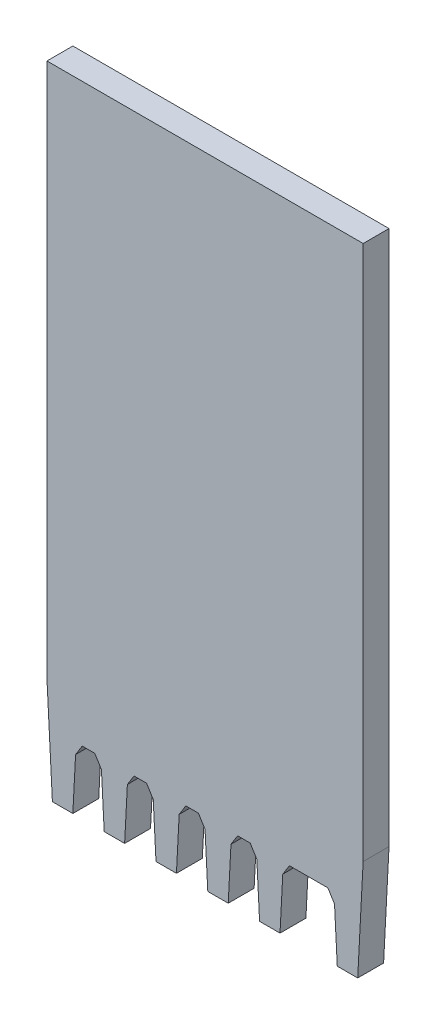
SolidWorks part; units mm, degrees
ref_plane "Front Plane" through (0, 0, 0) normal (0, 0, 1) x (1, 0, 0)
ref_plane "Top Plane" through (0, 0, 0) normal (0, 1, 0) x (1, 0, 0)
ref_plane "Right Plane" through (0, 0, 0) normal (1, 0, 0) x (0, 0, -1)
sketch "Sketch1" plane through (0, 0, 0) normal (0, 0, 1) x (1, 0, 0)
  line L0 (0, 0) -> (0, 37) construction
  line L1 (0, 37) -> (18.3124, 37) construction
  line L2 (18.3124, 37) -> (18.3124, 0) construction
  line L3 (18.3124, 0) -> (0, 0) construction
  line L4 (0, 3) -> (18.3124, 3) construction
  line L5 (0, 6) -> (18.3124, 6) construction
  line L6 (0.9062, 6) -> (0.9062, 0) construction
  line L7 (3.9062, 6) -> (3.9062, 0) construction
  line L8 (6.9062, 6) -> (6.9062, 0) construction
  line L9 (9.9062, 6) -> (9.9062, 0) construction
  line L10 (12.9062, 6) -> (12.9062, 0) construction
  line L11 (17.4062, 6) -> (17.4062, 0) construction
  line L12 (0.9062, 3) -> (3.9062, 3) construction
  line L13 (3.9062, 3) -> (6.9062, 3) construction
  line L14 (6.9062, 3) -> (9.9062, 3) construction
  line L15 (9.9062, 3) -> (12.9062, 3) construction
  line L16 (12.9062, 3) -> (17.4062, 3) construction
  line L17 (0.9062, 3) -> (0, 3) construction
  line L18 (17.4062, 3) -> (18.3124, 3) construction
  line L19 (2.4062, 3) -> (2.4062, 0) construction
  line L20 (5.4062, 3) -> (5.4062, 0) construction
  line L21 (8.4062, 3) -> (8.4062, 0) construction
  line L22 (11.4062, 3) -> (11.4062, 0) construction
  line L23 (15.1562, 3) -> (15.1562, 0) construction
  line L24 (14.4062, 3.75) -> (15.9062, 3.75) construction
  line L25 (0, 6) -> (0.3144, 0)
  line L26 (0.3144, 0) -> (1.4979, 0)
  line L27 (1.4979, 0) -> (1.6572, 3.0393)
  line L28 (3.1552, 3.0393) -> (3.3144, 0)
  line L29 (3.3144, 0) -> (4.4979, 0)
  line L30 (4.4979, 0) -> (4.6572, 3.0393)
  line L31 (6.1552, 3.0393) -> (6.3144, 0)
  line L32 (6.3144, 0) -> (7.4979, 0)
  line L33 (7.4979, 0) -> (7.6572, 3.0393)
  line L34 (9.1552, 3.0393) -> (9.3144, 0)
  line L35 (9.3144, 0) -> (10.4979, 0)
  line L36 (10.4979, 0) -> (10.6572, 3.0393)
  line L37 (12.1552, 3.0393) -> (12.3144, 0)
  line L38 (12.3144, 0) -> (13.4979, 0)
  line L39 (13.4979, 0) -> (13.6572, 3.0393)
  line L40 (16.6552, 3.0393) -> (16.8144, 0)
  line L41 (16.8144, 0) -> (17.9979, 0)
  line L42 (17.9979, 0) -> (18.3124, 6)
  line L44 (1.6572, 3.0393) -> (2.0426, 3.656)
  line L45 (0, 6) -> (0, 37)
  line L46 (0, 37) -> (18.3124, 37)
  line L47 (18.3124, 37) -> (18.3124, 6)
  line L48 (9.1562, 37) -> (9.1562, 6) construction
  line L49 (2.0426, 3.656) -> (2.7698, 3.656)
  line L50 (2.7698, 3.656) -> (3.1552, 3.0393)
  line L51 (4.6572, 3.0393) -> (5.0426, 3.656)
  line L52 (5.0426, 3.656) -> (5.7698, 3.656)
  line L53 (5.7698, 3.656) -> (6.1552, 3.0393)
  line L54 (7.6572, 3.0393) -> (8.0426, 3.656)
  line L55 (8.0426, 3.656) -> (8.7698, 3.656)
  line L56 (8.7698, 3.656) -> (9.1552, 3.0393)
  line L57 (10.6572, 3.0393) -> (11.0426, 3.656)
  line L58 (11.0426, 3.656) -> (11.7698, 3.656)
  line L59 (11.7698, 3.656) -> (12.1552, 3.0393)
  line L60 (13.6572, 3.0393) -> (14.0426, 3.656)
  line L61 (14.0426, 3.656) -> (16.2698, 3.656)
  line L62 (16.2698, 3.656) -> (16.6552, 3.0393)
  arc A0 (3.1552, 3.0393) -> (1.6572, 3.0393) centre (2.4062, 3) ccw construction
  arc A1 (6.1552, 3.0393) -> (4.6572, 3.0393) centre (5.4062, 3) ccw construction
  arc A2 (9.1552, 3.0393) -> (7.6572, 3.0393) centre (8.4062, 3) ccw construction
  arc A3 (12.1552, 3.0393) -> (10.6572, 3.0393) centre (11.4062, 3) ccw construction
  arc A4 (13.6572, 3.0393) -> (14.4062, 3.75) centre (14.4062, 3) cw construction
  arc A5 (16.6552, 3.0393) -> (15.9062, 3.75) centre (15.9062, 3) ccw construction
  dimension "D7" = 0.75
  dimension "D1" = 3
  dimension "D2" = 6
  dimension "D3" = 31
  dimension "D4" = 3
  dimension "D6" = 4.5
  dimension "D8" = 3
  dimension "D9" = 18.3124
  dimension "D10" = 37
extrude "Boss-Extrude1" add sketch "Sketch1" along normal blind 1.5
sketch "Sketch3" plane through (0, 0, 0) normal (0, 0, 1) x (1, 0, 0)
  line L0 (-0.4005, 6) -> (18.7129, 6)
  line L1 (18.7129, 3) -> (-0.4005, 3) construction
  line L2 (-0.4005, 0) -> (18.7129, 0) construction
  line L3 (-0.4005, -0.5) -> (18.7129, -0.5) construction
  line L4 (18.7129, -0.5) -> (18.7129, 6) construction
  line L5 (-0.4005, 6) -> (-0.4005, -0.5) construction
  line L6 (18.3124, 0) -> (0, 0) construction
  line L7 (0, 3) -> (18.3124, 3) construction
  line L8 (0, 6) -> (18.3124, 6) construction
  line L9 (0.3407, -0.5) -> (0, 6) construction
  line L10 (18.3124, 6) -> (17.9717, -0.5) construction
  line L11 (17.9979, 0) -> (18.3124, 6) construction
  line L12 (0, 6) -> (0.3144, 0) construction
  line L13 (5.4062, 6) -> (5.4062, -0.5) construction
  line L14 (3.9062, 6) -> (3.9062, -0.5) construction
  line L15 (5.4062, 3) -> (5.4062, 0) construction
  line L16 (3.1572, 3) -> (3.3407, -0.5) construction
  line L17 (2.7567, 3) -> (2.9401, -0.5)
  line L18 (3.1552, 3.0393) -> (3.3144, 0) construction
  line L19 (2.9401, -0.5) -> (4.8723, -0.5)
  line L20 (4.8723, -0.5) -> (5.0557, 3)
  line L21 (2.8484, 1.25) -> (3.2478, 1.2709) construction
  line L22 (5.9401, -0.5) -> (5.7567, 3)
  line L26 (7.8723, -0.5) -> (5.9401, -0.5)
  line L27 (8.0557, 3) -> (7.8723, -0.5)
  line L30 (2.4062, -0.5) -> (2.4062, 6) construction
  line L31 (2.4062, 3) -> (2.4062, 0) construction
  line L32 (8.4062, 6) -> (8.4062, -0.5) construction
  line L34 (11.4062, -0.5) -> (11.4062, 6) construction
  line L35 (15.1562, -0.5) -> (15.1562, 6) construction
  line L36 (8.4062, 3) -> (8.4062, 0) construction
  line L37 (11.4062, 3) -> (11.4062, 0) construction
  line L38 (15.1562, 3) -> (15.1562, 0) construction
  line L39 (10.8723, -0.5) -> (11.0557, 3)
  line L40 (8.9401, -0.5) -> (10.8723, -0.5)
  line L41 (8.7567, 3) -> (8.9401, -0.5)
  line L42 (11.9401, -0.5) -> (11.7567, 3)
  line L43 (13.8723, -0.5) -> (11.9401, -0.5)
  line L44 (14.0557, 3) -> (13.8723, -0.5)
  line L45 (16.4401, -0.5) -> (18.3723, -0.5)
  line L46 (16.2567, 3) -> (16.4401, -0.5)
  line L47 (18.3723, -0.5) -> (18.7129, 6)
  line L48 (1.8723, -0.5) -> (-0.0599, -0.5)
  line L49 (2.0557, 3) -> (1.8723, -0.5)
  line L50 (-0.0599, -0.5) -> (-0.4005, 6)
  line L51 (16.2567, 3) -> (14.0557, 3)
  line L52 (11.7567, 3) -> (11.0557, 3)
  line L53 (8.7567, 3) -> (8.0557, 3)
  line L54 (5.7567, 3) -> (5.0557, 3)
  line L55 (2.7567, 3) -> (2.0557, 3)
  dimension "D1" = 0.5
  dimension "D2" = 0.4
ref_plane "Plane1" through (3.9062, 0, 0) normal (1, 0, 0) x (0, 0, -1)
sketch "Sketch4" plane through (3.9062, 0, 0) normal (1, 0, 0) x (0, 0, -1)
  line L0 (0, 6) -> (0, -0.5) construction
  line L1 (0.6, 6) -> (-2.1, 6) construction
  line L2 (0.6, 6) -> (0.6, -0.5) construction
  line L3 (0.6, -0.5) -> (-2.1, -0.5) construction
  line L4 (-2.1, 6) -> (-2.1, -0.5) construction
  line L5 (-0.75, -0.5) -> (-0.75, 6) construction
  line L6 (-1.5, 6) -> (-1.5, -0.5) construction
  line L7 (0.6, 2.4005) -> (-2.1, 2.4005) construction
  line L8 (0.3, 6) -> (0.3, -0.5) construction
  line L9 (0.6, 2.4005) -> (3.846, 6) construction
  line L10 (2.2302, 6) -> (0.6, 4.1923) construction
  line L11 (0.6, 4.1923) -> (1.7139, 3.1878) construction
  line L12 (1.7139, 3.1878) -> (4.25, 6)
  line L13 (4.25, 6) -> (0.6, 6) construction
  line L14 (0.3, 1) -> (-1.8, 1) construction
  line L15 (-2.1, 0) -> (0.6, 0) construction
  line L16 (1.7139, 3.1878) -> (1.4912, 3.3887)
  line L17 (1.4912, 3.3887) -> (0.6, 2.4005)
  line L18 (-3.2139, 3.1878) -> (-5.75, 6)
  line L19 (-3.2139, 3.1878) -> (-2.9912, 3.3887)
  line L20 (-2.9912, 3.3887) -> (-2.1, 2.4005)
  line L21 (-2.1, 6) -> (-5.75, 6) construction
  line L22 (0.6, 3.0724) -> (3.2401, 6) construction
  arc A0 (0.4965, 2.2224) -> (0.6, -0.5) centre (4.2, 1) ccw
  arc A1 (0.6, 2.4005) -> (0.4965, 2.2224) centre (0.9713, 2.0656) ccw
  arc A2 (-2.1, 2.4005) -> (-1.9965, 2.2224) centre (-2.4713, 2.0656) cw
  arc A3 (-1.9965, 2.2224) -> (-2.1, -0.5) centre (-5.7, 1) cw
  dimension "D6" = 0.5
  dimension "D1" = 0.6
  dimension "D2" = 0.3
  dimension "D3" = 1.5
  dimension "D4" = 1
  dimension "D5" = 0.3
  dimension "D7" = 10
sketch "Sketch5" plane through (0, 0, 0) normal (1, 0, 0) x (0, 0, -1)
  line L0 (2.2302, 6) -> (0.6, 4.1923) construction
  line L1 (0.6, 4.1923) -> (1.7139, 3.1878) construction
  line L2 (1.7139, 3.1878) -> (4.25, 6) construction
  line L3 (2.2302, 6) -> (0.6, 4.1923) construction
  line L4 (0.6, 4.1923) -> (1.7139, 3.1878) construction
  line L5 (1.7139, 3.1878) -> (4.25, 6) construction
ref_plane "Plane2" through (0, 2.6105, -2.3541) normal (0, 0.7426, -0.6697) x (1, 0, 0)
sketch "Sketch6" plane through (0, 2.6105, -2.3541) normal (0, 0.7426, -0.6697) x (1, 0, 0)
  line L1 (3.9062, -2.362) -> (3.9062, -0.862) construction
  line L2 (3.9062, -2.362) -> (3.9062, -5.0612) construction
  line L3 (4.6562, -5.0612) -> (3.1562, -5.0612)
  line L4 (4.6562, -1.612) -> (3.1562, -1.612) construction
  line L5 (3.1562, -1.612) -> (3.1562, -5.0612)
  line L6 (4.6562, -1.612) -> (4.6562, -5.0612)
  line L10 (2.4062, -5.0612) -> (15.1562, -5.0612) construction
  line L11 (15.1562, -5.0612) -> (15.1562, -0.862) construction
  line L12 (15.1562, -0.862) -> (2.4062, -0.862) construction
  line L13 (2.4062, -0.862) -> (2.4062, -5.0612) construction
  line L14 (15.1562, 0.3349) -> (15.1562, -4.0182) construction
  line L15 (2.4062, 0.3349) -> (2.4062, -4.0182) construction
  line L16 (11.4062, -5.0612) -> (11.4062, -0.862) construction
  line L17 (8.4062, -5.0612) -> (8.4062, -0.862) construction
  line L18 (5.4062, -5.0612) -> (5.4062, -0.862) construction
  line L19 (5.4062, -4.0182) -> (5.4062, 0.3349) construction
  line L20 (8.4062, -4.0182) -> (8.4062, 0.3349) construction
  line L21 (11.4062, 0.3349) -> (11.4062, -4.0182) construction
  line L22 (0.1562, -1.612) -> (0.1562, -5.0612)
  line L23 (0.1562, -5.0612) -> (1.6562, -5.0612)
  line L24 (1.6562, -1.612) -> (1.6562, -5.0612)
  line L25 (7.6562, -1.612) -> (7.6562, -5.0612)
  line L26 (6.1562, -5.0612) -> (7.6562, -5.0612)
  line L27 (6.1562, -1.612) -> (6.1562, -5.0612)
  line L28 (10.6562, -1.612) -> (10.6562, -5.0612)
  line L29 (10.6562, -5.0612) -> (9.1562, -5.0612)
  line L30 (9.1562, -1.612) -> (9.1562, -5.0612)
  line L31 (13.6562, -1.612) -> (13.6562, -5.0612)
  line L32 (12.1562, -5.0612) -> (13.6562, -5.0612)
  line L33 (12.1562, -1.612) -> (12.1562, -5.0612)
  line L34 (18.1562, -1.612) -> (18.1562, -5.0612)
  line L35 (18.1562, -5.0612) -> (16.6562, -5.0612)
  line L36 (16.6562, -1.612) -> (16.6562, -5.0612)
  circle A0 centre (3.9062, -1.612) radius 0.75 construction
  arc A1 (4.6562, -1.612) -> (3.1562, -1.612) centre (3.9062, -1.612) ccw
  arc A2 (0.1562, -1.612) -> (1.6562, -1.612) centre (0.9062, -1.612) cw
  arc A3 (6.1562, -1.612) -> (7.6562, -1.612) centre (6.9062, -1.612) cw
  arc A4 (10.6562, -1.612) -> (9.1562, -1.612) centre (9.9062, -1.612) ccw
  arc A5 (12.1562, -1.612) -> (13.6562, -1.612) centre (12.9062, -1.612) cw
  arc A6 (18.1562, -1.612) -> (16.6562, -1.612) centre (17.4062, -1.612) ccw
ref_plane "Plane3" through (0, 1.6223, -1.463) normal (0, 0.7426, -0.6697) x (1, 0, 0)
sketch "Sketch7" plane through (0, 1.6223, -1.463) normal (0, 0.7426, -0.6697) x (1, 0, 0)
  line L0 (3.1562, -1.612) -> (3.1562, -5.0612) construction
  line L1 (4.6562, -5.0612) -> (3.1562, -5.0612) construction
  line L2 (4.6562, -1.612) -> (4.6562, -5.0612) construction
  line L3 (3.1562, -1.612) -> (3.1562, -5.0612) construction
  line L4 (4.6562, -5.0612) -> (3.1562, -5.0612) construction
  line L5 (4.6562, -1.612) -> (4.6562, -5.0612) construction
  line L6 (3.9062, -0.862) -> (3.9062, -5.0612) construction
  line L7 (4.6562, -1.612) -> (3.1562, -1.612) construction
  line L8 (4.6562, -2.362) -> (3.1562, -2.362) construction
  line L9 (3.4562, -1.612) -> (3.4562, -2.362)
  line L10 (3.4562, -2.362) -> (4.3562, -2.362)
  line L11 (4.3562, -2.362) -> (4.3562, -1.612)
  line L12 (2.4062, -0.862) -> (2.4062, -5.0612) construction
  line L13 (2.4062, -5.0612) -> (15.1562, -5.0612) construction
  line L14 (15.1562, -0.862) -> (2.4062, -0.862) construction
  line L15 (5.4062, -5.0612) -> (5.4062, -0.862) construction
  line L16 (8.4062, -5.0612) -> (8.4062, -0.862) construction
  line L17 (11.4062, -5.0612) -> (11.4062, -0.862) construction
  line L18 (15.1562, -5.0612) -> (15.1562, -0.862) construction
  line L19 (2.4062, -0.862) -> (2.4062, -5.0612) construction
  line L20 (2.4062, -5.0612) -> (15.1562, -5.0612) construction
  line L21 (15.1562, -0.862) -> (2.4062, -0.862) construction
  line L22 (5.4062, -5.0612) -> (5.4062, -0.862) construction
  line L23 (8.4062, -5.0612) -> (8.4062, -0.862) construction
  line L24 (11.4062, -5.0612) -> (11.4062, -0.862) construction
  line L25 (15.1562, -5.0612) -> (15.1562, -0.862) construction
  line L26 (0.4562, -2.362) -> (0.4562, -1.612)
  line L27 (1.3562, -2.362) -> (0.4562, -2.362)
  line L28 (1.3562, -1.612) -> (1.3562, -2.362)
  line L29 (7.3562, -2.362) -> (6.4562, -2.362)
  line L30 (7.3562, -1.612) -> (7.3562, -2.362)
  line L31 (6.4562, -2.362) -> (6.4562, -1.612)
  line L32 (9.4562, -1.612) -> (9.4562, -2.362)
  line L33 (10.3562, -2.362) -> (10.3562, -1.612)
  line L34 (9.4562, -2.362) -> (10.3562, -2.362)
  line L35 (13.3562, -1.612) -> (13.3562, -2.362)
  line L36 (12.4562, -2.362) -> (12.4562, -1.612)
  line L37 (13.3562, -2.362) -> (12.4562, -2.362)
  line L38 (16.9562, -1.612) -> (16.9562, -2.362)
  line L39 (17.8562, -2.362) -> (17.8562, -1.612)
  line L40 (16.9562, -2.362) -> (17.8562, -2.362)
  arc A0 (4.6562, -1.612) -> (3.1562, -1.612) centre (3.9062, -1.612) ccw construction
  arc A1 (4.6562, -1.612) -> (3.1562, -1.612) centre (3.9062, -1.612) ccw construction
  circle A2 centre (3.9062, -1.612) radius 0.45 construction
  arc A3 (4.3562, -1.612) -> (3.4562, -1.612) centre (3.9062, -1.612) ccw
  arc A4 (0.4562, -1.612) -> (1.3562, -1.612) centre (0.9062, -1.612) cw
  arc A5 (6.4562, -1.612) -> (7.3562, -1.612) centre (6.9062, -1.612) cw
  arc A6 (10.3562, -1.612) -> (9.4562, -1.612) centre (9.9062, -1.612) ccw
  arc A7 (12.4562, -1.612) -> (13.3562, -1.612) centre (12.9062, -1.612) cw
  arc A8 (17.8562, -1.612) -> (16.9562, -1.612) centre (17.4062, -1.612) ccw
ref_plane "bisect" through (0, 0, 0.75) normal (0, 0, 1) x (1, 0, 0)
ref_plane "insert_surface" through (0, 6, 0) normal (0, 1, 0) x (1, 0, 0)
sketch "Sketch8" plane through (0, 6, 0) normal (0, 1, 0) x (1, 0, 0)
  line L0 (18.7129, -0.75) -> (-0.4005, -0.75) construction
  line L1 (-0.4005, 0.6) -> (18.7129, 0.6)
  line L2 (-0.4005, 0.6) -> (-0.4005, -2.1)
  line L3 (-0.4005, -2.1) -> (18.7129, -2.1)
  line L4 (18.7129, 0.6) -> (18.7129, -2.1)
  line L5 (9.1562, 0.6) -> (9.1562, -2.1) construction
  line L6 (0, 0) -> (18.3124, 0) construction
  line L7 (0, 0) -> (0, -1.5) construction
  line L8 (0, -1.5) -> (18.3124, -1.5) construction
  line L9 (18.3124, 0) -> (18.3124, -1.5) construction
  line L10 (18.7129, 0.3) -> (-0.4005, 0.3) construction
  line L11 (18.7129, -1.8) -> (-0.4005, -1.8) construction
sketch "Sketch9" plane through (0, 0, 0) normal (0, 0, 1) x (1, 0, 0)
  line L0 (18.3723, -0.5) -> (18.7129, 6) construction
  line L1 (-0.4005, 6) -> (18.7129, 6) construction
  line L2 (-0.0599, -0.5) -> (-0.4005, 6) construction
  line L3 (1.8723, -0.5) -> (-0.0599, -0.5) construction
  line L4 (2.0557, 3) -> (1.8723, -0.5) construction
  line L5 (2.7567, 3) -> (2.0557, 3) construction
  line L6 (2.7567, 3) -> (2.9401, -0.5) construction
  line L7 (2.9401, -0.5) -> (4.8723, -0.5) construction
  line L8 (4.8723, -0.5) -> (5.0557, 3) construction
  line L9 (5.7567, 3) -> (5.0557, 3) construction
  line L10 (5.9401, -0.5) -> (5.7567, 3) construction
  line L11 (7.8723, -0.5) -> (5.9401, -0.5) construction
  line L12 (8.0557, 3) -> (7.8723, -0.5) construction
  line L13 (8.7567, 3) -> (8.0557, 3) construction
  line L14 (8.7567, 3) -> (8.9401, -0.5) construction
  line L15 (8.9401, -0.5) -> (10.8723, -0.5) construction
  line L16 (10.8723, -0.5) -> (11.0557, 3) construction
  line L17 (11.7567, 3) -> (11.0557, 3) construction
  line L18 (11.9401, -0.5) -> (11.7567, 3) construction
  line L19 (13.8723, -0.5) -> (11.9401, -0.5) construction
  line L20 (14.0557, 3) -> (13.8723, -0.5) construction
  line L21 (16.2567, 3) -> (14.0557, 3) construction
  line L22 (16.2567, 3) -> (16.4401, -0.5) construction
  line L23 (16.4401, -0.5) -> (18.3723, -0.5) construction
  line L24 (18.3723, -0.5) -> (18.7129, 6)
  line L25 (-0.4005, 6) -> (18.7129, 6) construction
  line L26 (-0.0599, -0.5) -> (-0.4005, 6)
  line L27 (1.8723, -0.5) -> (-0.0599, -0.5)
  line L28 (2.0557, 3) -> (1.8723, -0.5)
  line L29 (2.7567, 3) -> (2.0557, 3) construction
  line L30 (2.7567, 3) -> (2.9401, -0.5)
  line L31 (2.9401, -0.5) -> (4.8723, -0.5)
  line L32 (4.8723, -0.5) -> (5.0557, 3)
  line L33 (5.7567, 3) -> (5.0557, 3) construction
  line L34 (5.9401, -0.5) -> (5.7567, 3)
  line L35 (7.8723, -0.5) -> (5.9401, -0.5)
  line L36 (8.0557, 3) -> (7.8723, -0.5)
  line L37 (8.7567, 3) -> (8.0557, 3) construction
  line L38 (8.7567, 3) -> (8.9401, -0.5)
  line L39 (8.9401, -0.5) -> (10.8723, -0.5)
  line L40 (10.8723, -0.5) -> (11.0557, 3)
  line L41 (11.7567, 3) -> (11.0557, 3) construction
  line L42 (11.9401, -0.5) -> (11.7567, 3)
  line L43 (13.8723, -0.5) -> (11.9401, -0.5)
  line L44 (14.0557, 3) -> (13.8723, -0.5)
  line L45 (16.2567, 3) -> (14.0557, 3) construction
  line L46 (16.2567, 3) -> (16.4401, -0.5)
  line L47 (16.4401, -0.5) -> (18.3723, -0.5)
  line L48 (16.2567, 3) -> (16.2567, 6)
  line L49 (14.0557, 3) -> (14.0557, 6)
  line L50 (11.7567, 3) -> (11.7567, 6)
  line L51 (18.7129, 6) -> (-0.4005, 6) construction
  line L52 (11.0557, 3) -> (11.0557, 6)
  line L53 (-0.4005, 6) -> (18.7129, 6) construction
  line L54 (8.7567, 3) -> (8.7567, 6)
  line L55 (8.0557, 3) -> (8.0557, 6)
  line L58 (5.7567, 3) -> (5.7567, 6)
  line L60 (5.0557, 3) -> (5.0557, 6)
  line L62 (15.1562, -0.5) -> (15.1562, 6) construction
  line L63 (15.1562, -0.5) -> (15.1562, 6) construction
  line L64 (2.7567, 3) -> (2.7567, 6)
  line L65 (2.0557, 3) -> (2.0557, 6)
  line L67 (18.7129, 6) -> (16.2567, 6)
  line L68 (14.0557, 6) -> (11.7567, 6)
  line L69 (11.0557, 6) -> (8.7567, 6)
  line L70 (8.0557, 6) -> (5.7567, 6)
  line L71 (5.0557, 6) -> (2.7567, 6)
  line L72 (2.0557, 6) -> (-0.4005, 6)
sketch "Sketch10" plane through (0, 6, 0) normal (0, 1, 0) x (1, 0, 0)
  line L0 (9.1562, -5) -> (9.1562, 0) construction
  line L1 (-0.8438, 5) -> (19.1562, 5)
  line L2 (-0.8438, 5) -> (-0.8438, -5)
  line L3 (-0.8438, -5) -> (19.1562, -5)
  line L4 (19.1562, 5) -> (19.1562, -5)
  line L5 (9.1562, 0) -> (9.1562, 5) construction
  line L6 (9.1562, 0) -> (19.1562, 0) construction
  line L7 (9.1562, 0) -> (-0.8438, 0) construction
  dimension "D1" = 10
  dimension "D2" = 20
